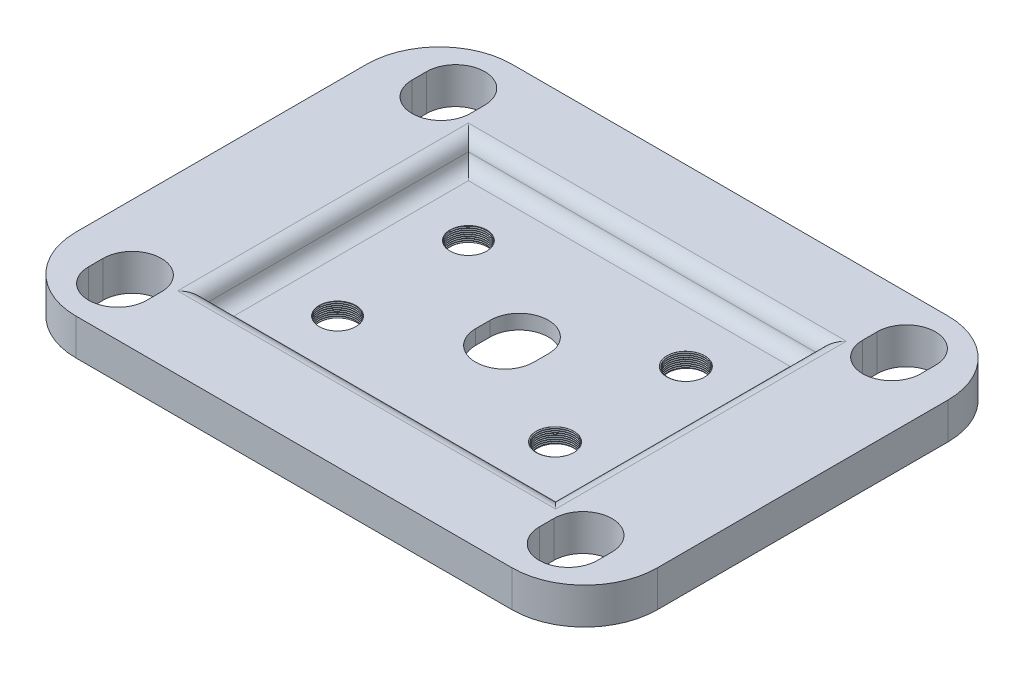
SolidWorks part; units mm, degrees
ref_plane "Front Plane" through (0, 0, 0) normal (0, 0, 1) x (1, 0, 0)
ref_plane "Top Plane" through (0, 0, 0) normal (0, 1, 0) x (1, 0, 0)
ref_plane "Right Plane" through (0, 0, 0) normal (1, 0, 0) x (0, 0, -1)
sketch "Sketch1" plane through (0, 0, 0) normal (0, 1, 0) x (1, 0, 0)
  line L0 (-31, 23.25) -> (-31, 21.25) construction
  line L1 (-40, -30) -> (40, -30)
  line L2 (-40, -30) -> (-40, 30)
  line L3 (-40, 30) -> (40, 30)
  line L4 (40, -30) -> (40, 30)
  line L5 (-40, -30) -> (40, 30) construction
  line L6 (-40, 30) -> (40, -30) construction
  line L7 (-24, -18) -> (24, -18)
  line L8 (-24, -18) -> (-24, 18)
  line L9 (-24, 18) -> (24, 18)
  line L10 (24, -18) -> (24, 18)
  line L11 (-24, -18) -> (24, 18) construction
  line L12 (-24, 18) -> (24, -18) construction
  line L13 (31, -23.25) -> (-31, -23.25) construction
  line L14 (31, -23.25) -> (31, 23.25) construction
  line L15 (31, 23.25) -> (-31, 23.25) construction
  line L16 (-31, -23.25) -> (-31, 23.25) construction
  line L17 (31, -23.25) -> (-31, 23.25) construction
  line L18 (31, 23.25) -> (-31, -23.25) construction
  line L19 (-27, 23.25) -> (-27, 21.25)
  line L20 (-35, 23.25) -> (-35, 21.25)
  line L21 (31, 23.25) -> (31, 21.25) construction
  line L22 (35, 23.25) -> (35, 21.25)
  line L23 (27, 23.25) -> (27, 21.25)
  line L24 (31, -23.25) -> (31, -21.25) construction
  line L25 (27, -23.25) -> (27, -21.25)
  line L26 (35, -23.25) -> (35, -21.25)
  line L27 (-31, -23.25) -> (-31, -21.25) construction
  line L28 (-35, -23.25) -> (-35, -21.25)
  line L29 (-27, -23.25) -> (-27, -21.25)
  arc A0 (-27, 23.25) -> (-35, 23.25) centre (-31, 23.25) ccw
  arc A1 (-35, 21.25) -> (-27, 21.25) centre (-31, 21.25) ccw
  arc A2 (35, 23.25) -> (27, 23.25) centre (31, 23.25) ccw
  arc A3 (27, 21.25) -> (35, 21.25) centre (31, 21.25) ccw
  arc A4 (27, -23.25) -> (35, -23.25) centre (31, -23.25) ccw
  arc A5 (35, -21.25) -> (27, -21.25) centre (31, -21.25) ccw
  arc A6 (-35, -23.25) -> (-27, -23.25) centre (-31, -23.25) ccw
  arc A7 (-27, -21.25) -> (-35, -21.25) centre (-31, -21.25) ccw
  point P0 (0, 0)
  point P6 (0, 0)
  point P11 (0, 0)
  point P16 (-31, 22.25)
  point P22 (31, 22.25)
  point P28 (31, -22.25)
  point P34 (-31, -22.25)
  dimension "D7" = 4
  dimension "D1" = 80
  dimension "D2" = 60
  dimension "D3" = 9
  dimension "D5" = 2
  dimension "D6" = 48
extrude "Boss-Extrude1" add sketch "Sketch1" along normal blind 5
extrude "Boss-Extrude2" add sketch "Sketch1<2>" along normal blind 2 contours L7 L10 L9 L8 region at (0, 0, 0)
sketch "Sketch1<2>" plane through (0, 0, 0) normal (0, 1, 0) x (1, 0, 0) same geometry as "Sketch1"
sketch "Sketch2" plane through (0, 2, 0) normal (0, 1, 0) x (1, 0, 0)
  line L0 (0, 1) -> (0, -1) construction
  line L1 (4, 1) -> (4, -1)
  line L2 (-4, 1) -> (-4, -1)
  arc A0 (4, 1) -> (-4, 1) centre (0, 1) ccw
  arc A1 (-4, -1) -> (4, -1) centre (0, -1) ccw
  point P2 (0, 0)
  dimension "D2" = 4
  dimension "D1" = 2
extrude "Cut-Extrude1" cut sketch "Sketch2" against normal through all
sketch "Sketch3" plane through (0, 2, 0) normal (0, 1, 0) x (1, 0, 0)
  line L8 (-15, -9) -> (15, -9)
  line L9 (15, -9) -> (15, 9)
  line L10 (15, 9) -> (-15, 9)
  line L11 (-15, 9) -> (-15, -9)
  line L12 (-15, -9) -> (15, -9) construction
  line L13 (15, -9) -> (15, 9) construction
  line L14 (15, 9) -> (-15, 9) construction
  line L15 (-15, 9) -> (-15, -9) construction
  dimension "D1" = 9
hole_wizard "Ø5.0 (5) Diameter Hole1" positions "Sketch4" profile "Sketch5" hole size "Ø5.0" standard "AS" end condition through all
sketch "Sketch4" plane through (0, 2, 0) normal (0, 1, 0) x (1, 0, 0)
  point P0 (-15, 9)
  point P3 (-15, -9)
  point P6 (15, -9)
  point P9 (15, 9)
sketch "Sketch5" plane through (-15, 2, -9) normal (1, 0, 0) x (0, 0, 1)
  line L0 (0, 0) -> (0, 2)
  line L1 (0, 2) -> (2.5, 2)
  line L2 (2.5, 2) -> (2.5, 0.025)
  line L3 (2.5, 0.025) -> (2.525, 0)
  line L5 (2.525, 0) -> (0, 0)
  line L6 (-2.5, 0.025) -> (-2.525, 0) construction
  line L11 (0, -6.35) -> (0, 107.95) construction
  dimension "Thru Hole Dia." = 5
  dimension "Thru Hole Depth" = 2
  dimension "Near C'Sink Dia." = 5.05
  dimension "Near C'Sink Angle" = 90
thread "Thread1" pitch 0.25 method cut profile "Thread Profile1" start angle 0, offset 0, length 10, pitch 0.25, diameter 5
ref_plane "Plane1" through (-17.5, 1.975, 9) normal (0, 0, 1) x (-1, 0, 0)
sketch "Thread Profile1" plane through (-17.5, 1.975, 9) normal (0, 0, 1) x (-1, 0, 0)
  line L0 (0, 0) -> (0, 0.25) construction
  line L1 (0, 0) -> (0.1353, 0.0781)
  line L2 (0.1353, 0.0781) -> (0.1353, 0.1094)
  line L3 (0.1353, 0.1094) -> (0, 0.1875)
  line L4 (0.1353, 0.0937) -> (0, 0.0937) construction
  line L11 (0, 0) -> (0, 0.1875)
  point P2 (0, 0)
  dimension "Pitch" = 0.25
  dimension "Profile_Angle" = 60
  dimension "Profile_Land" = 0.0312
  dimension "Profile_Height" = 0.1353
thread "Thread2" pitch 0.25 method cut profile "Thread Profile2" start angle 0, offset 0, length 10, pitch 0.25, diameter 5
ref_plane "Plane2" through (-17.5, 1.975, -9) normal (0, 0, 1) x (-1, 0, 0)
sketch "Thread Profile2" plane through (-17.5, 1.975, -9) normal (0, 0, 1) x (-1, 0, 0)
  line L0 (0, 0) -> (0, 0.25) construction
  line L1 (0, 0) -> (0.1353, 0.0781)
  line L2 (0.1353, 0.0781) -> (0.1353, 0.1094)
  line L3 (0.1353, 0.1094) -> (0, 0.1875)
  line L4 (0.1353, 0.0937) -> (0, 0.0937) construction
  line L11 (0, 0) -> (0, 0.1875)
  point P2 (0, 0)
  dimension "Pitch" = 0.25
  dimension "Profile_Angle" = 60
  dimension "Profile_Land" = 0.0312
  dimension "Profile_Height" = 0.1353
thread "Thread3" pitch 0.25 method cut profile "Thread Profile3" start angle 0, offset 0, length 10, pitch 0.25, diameter 5
ref_plane "Plane3" through (17.5, 0, -9) normal (0, 0, 1) x (1, 0, 0)
sketch "Thread Profile3" plane through (17.5, 0, -9) normal (0, 0, 1) x (1, 0, 0)
  line L0 (0, 0) -> (0, 0.25) construction
  line L1 (0, 0) -> (0.1353, 0.0781)
  line L2 (0.1353, 0.0781) -> (0.1353, 0.1094)
  line L3 (0.1353, 0.1094) -> (0, 0.1875)
  line L4 (0.1353, 0.0937) -> (0, 0.0937) construction
  line L11 (0, 0) -> (0, 0.1875)
  point P2 (0, 0)
  dimension "Pitch" = 0.25
  dimension "Profile_Angle" = 60
  dimension "Profile_Land" = 0.0312
  dimension "Profile_Height" = 0.1353
thread "Thread4" pitch 0.25 method cut profile "Thread Profile4" start angle 0, offset 0, length 10, pitch 0.25, diameter 5
ref_plane "Plane4" through (17.5, 0, 9) normal (0, 0, 1) x (1, 0, 0)
sketch "Thread Profile4" plane through (17.5, 0, 9) normal (0, 0, 1) x (1, 0, 0)
  line L0 (0, 0) -> (0, 0.25) construction
  line L1 (0, 0) -> (0.1353, 0.0781)
  line L2 (0.1353, 0.0781) -> (0.1353, 0.1094)
  line L3 (0.1353, 0.1094) -> (0, 0.1875)
  line L4 (0.1353, 0.0937) -> (0, 0.0937) construction
  line L11 (0, 0) -> (0, 0.1875)
  point P2 (0, 0)
  dimension "Pitch" = 0.25
  dimension "Profile_Angle" = 60
  dimension "Profile_Land" = 0.0312
  dimension "Profile_Height" = 0.1353
fillet "Fillet1" radius 10 4 edges at (40, 2.5, 30) (40, 2.5, -30) (-40, 2.5, -30) (-40, 2.5, 30)
fillet "Fillet2" radius 2 2 edges at (24, 5, 0) (0, 5, -18)
fillet "Fillet3" radius 2 2 edges at (1, 5, 18) (-24, 5, -1)
fillet "Fillet4" radius 2 4 edges at (-24, 2, 0) (0, 2, 18) (24, 2, 0) (0, 2, -18)
